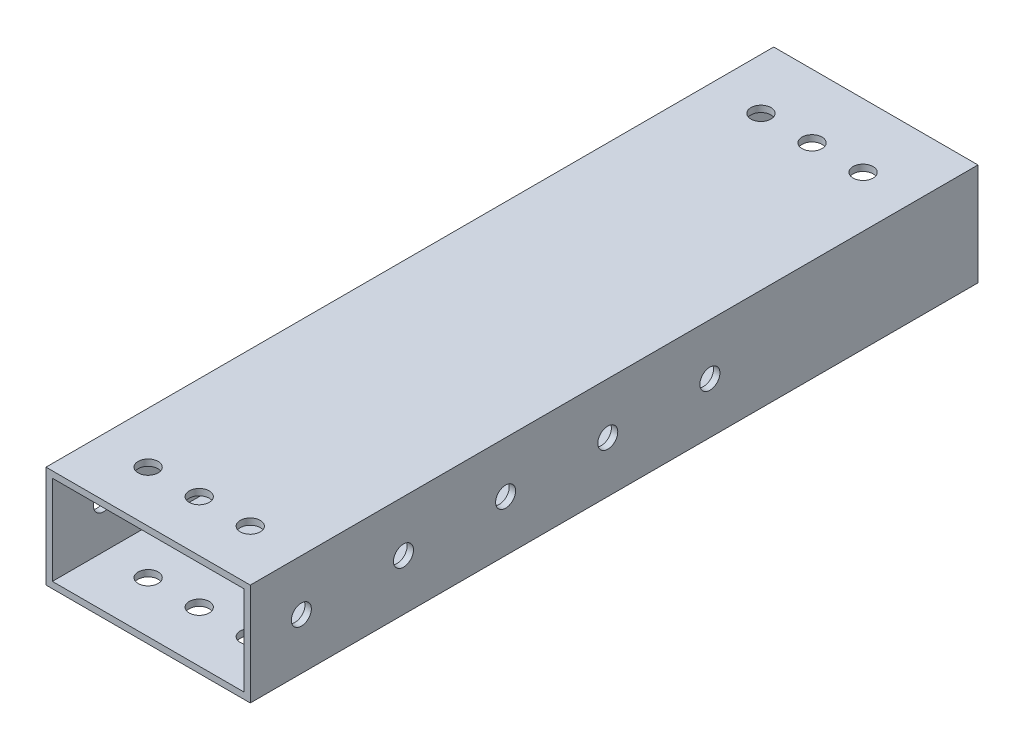
SolidWorks part; units mm, degrees
material "6061-T6 (SS)"
ref_plane "Front Plane" through (0, 0, 0) normal (0, 0, 1) x (1, 0, 0)
ref_plane "Top Plane" through (0, 0, 0) normal (0, 1, 0) x (1, 0, 0)
ref_plane "Right Plane" through (0, 0, 0) normal (1, 0, 0) x (0, 0, -1)
sketch "Sketch1" plane through (0, 0, 0) normal (0, 0, 1) x (1, 0, 0)
  line L1 (-25.4, -12.7) -> (25.4, -12.7)
  line L2 (-25.4, -12.7) -> (-25.4, 12.7)
  line L3 (-25.4, 12.7) -> (25.4, 12.7)
  line L4 (25.4, -12.7) -> (25.4, 12.7)
  line L5 (-25.4, -12.7) -> (25.4, 12.7) construction
  line L6 (-25.4, 12.7) -> (25.4, -12.7) construction
  line L7 (-23.8125, -11.1125) -> (23.8125, -11.1125)
  line L8 (-23.8125, -11.1125) -> (-23.8125, 11.1125)
  line L9 (-23.8125, 11.1125) -> (23.8125, 11.1125)
  line L10 (23.8125, -11.1125) -> (23.8125, 11.1125)
  line L11 (-23.8125, -11.1125) -> (23.8125, 11.1125) construction
  line L12 (-23.8125, 11.1125) -> (23.8125, -11.1125) construction
  point P0 (0, 0)
  point P6 (0, 0)
  dimension "D1" = 50.8
  dimension "D2" = 25.4
  dimension "D3" = 1.5875
  dimension "D4" = 1.5875
extrude "Boss-Extrude1" add sketch "Sketch1" along normal blind 180.975
sketch "Sketch2" plane through (0, 12.7, 0) normal (0, 1, 0) x (1, 0, 0)
  line L0 (25.4, 0) -> (-25.4, 0) construction
  line L3 (25.4, -180.975) -> (-25.4, -180.975) construction
  circle A0 centre (-12.7, -15.875) radius 2.4892
  circle A1 centre (0, -15.875) radius 2.4892
  circle A2 centre (12.7, -15.875) radius 2.4892
  circle A3 centre (-12.7, -168.275) radius 2.4892
  circle A4 centre (0, -168.275) radius 2.4892
  circle A5 centre (12.7, -168.275) radius 2.4892
  dimension "D1" = 4.9784
  dimension "D2" = 15.875
  dimension "D3" = 12.7
  dimension "D4" = 12.7
  dimension "D5" = 12.7
extrude "Cut-Extrude1" cut sketch "Sketch2" against normal through all
sketch "Sketch3" plane through (25.4, 0, 0) normal (1, 0, 0) x (0, 0, -1)
  line L0 (-180.975, -12.7) -> (-180.975, 12.7) construction
  circle A0 centre (-168.275, 0) radius 2.4892
  circle A1 centre (-142.875, 0) radius 2.4892
  circle A2 centre (-117.475, 0) radius 2.4892
  circle A3 centre (-92.075, 0) radius 2.4892
  circle A4 centre (-66.675, 0) radius 2.4892
  point P5 (-180.975, 0)
  dimension "D1" = 4.9784
  dimension "D2" = 12.7
  dimension "D4" = 25.4
  dimension "D3" = 5
extrude "Cut-Extrude2" cut sketch "Sketch3" against normal through all
